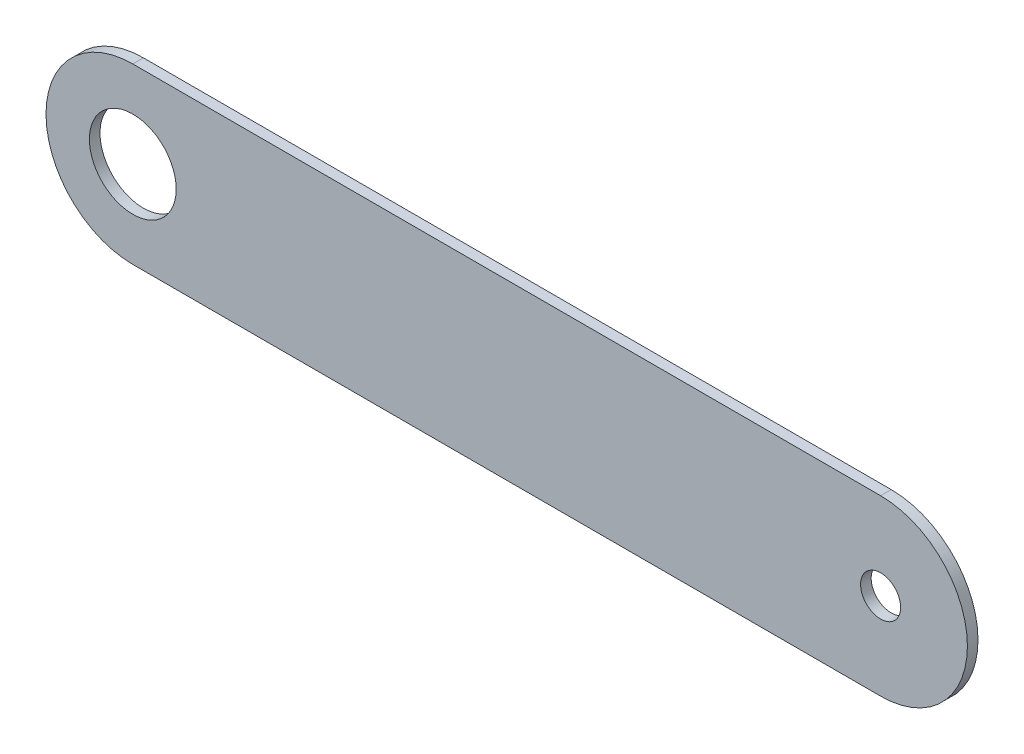
SolidWorks part; units mm, degrees
material "6061 Alloy"
ref_plane "Front Plane" through (0, 0, 0) normal (0, 0, 1) x (1, 0, 0)
ref_plane "Top Plane" through (0, 0, 0) normal (0, 1, 0) x (1, 0, 0)
ref_plane "Right Plane" through (0, 0, 0) normal (1, 0, 0) x (0, 0, -1)
sketch "Sketch1" plane through (0, 0, 0) normal (0, 0, 1) x (1, 0, 0)
  line L0 (0, 13) -> (112, 13)
  line L1 (0, -13) -> (112, -13)
  circle A0 centre (0, 0) radius 6.5
  arc A1 (0, 13) -> (0, -13) centre (0, 0) ccw
  circle A2 centre (112, 0) radius 3
  arc A3 (112, -13) -> (112, 13) centre (112, 0) ccw
  dimension "D1" = 112
  dimension "D2" = 13
  dimension "D3" = 26
  dimension "D4" = 6
extrude "Boss-Extrude1" add sketch "Sketch1" along normal blind 1.5875
